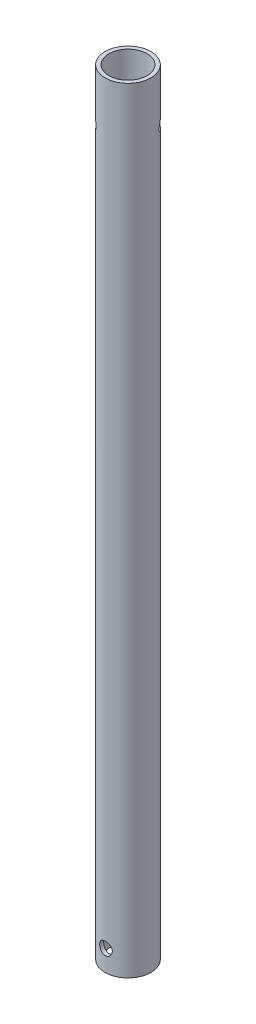
SolidWorks part; units mm, degrees
ref_plane "Front Plane" through (0, 0, 0) normal (0, 0, 1) x (1, 0, 0)
ref_plane "Top Plane" through (0, 0, 0) normal (0, 1, 0) x (1, 0, 0)
ref_plane "Right Plane" through (0, 0, 0) normal (1, 0, 0) x (0, 0, -1)
sketch "Sketch1" plane through (0, 0, 0) normal (0, 1, 0) x (1, 0, 0)
  circle A0 centre (0, 0) radius 5
  circle A1 centre (0, 0) radius 6
  dimension "D1" = 10
  dimension "D2" = 12
extrude "Boss-Extrude1" add sketch "Sketch1" along normal blind 203.2
sketch "Sketch2" plane through (0, 0, 0) normal (0, 0, 1) x (1, 0, 0)
  circle A0 centre (0, 5.5) radius 1.65
  point P2 (0, 0)
  dimension "D1" = 3.3
  dimension "D2" = 5.5
extrude "Cut-Extrude1" cut sketch "Sketch2" against normal through all both and the other way through all
ref_plane "Plane2" through (-1.5454, 0, 1.347) normal (-0.7538, 0, 0.6571) x (0.6571, 0, 0.7538)
sketch "Sketch5" plane through (-1.5454, 0, 1.347) normal (-0.7538, 0, 0.6571) x (0.6571, 0, 0.7538)
  arc A0 (0, 188.45) -> (0, 190.95) centre (0, 189.7) ccw construction
  arc A1 (0, 190.95) -> (0, 188.45) centre (0, 189.7) ccw construction
  arc A2 (0, 188.45) -> (0, 190.95) centre (0, 189.7) ccw
  arc A3 (0, 190.95) -> (0, 188.45) centre (0, 189.7) ccw
extrude "Cut-Extrude2" cut sketch "Sketch5" against normal through all both and the other way through all
